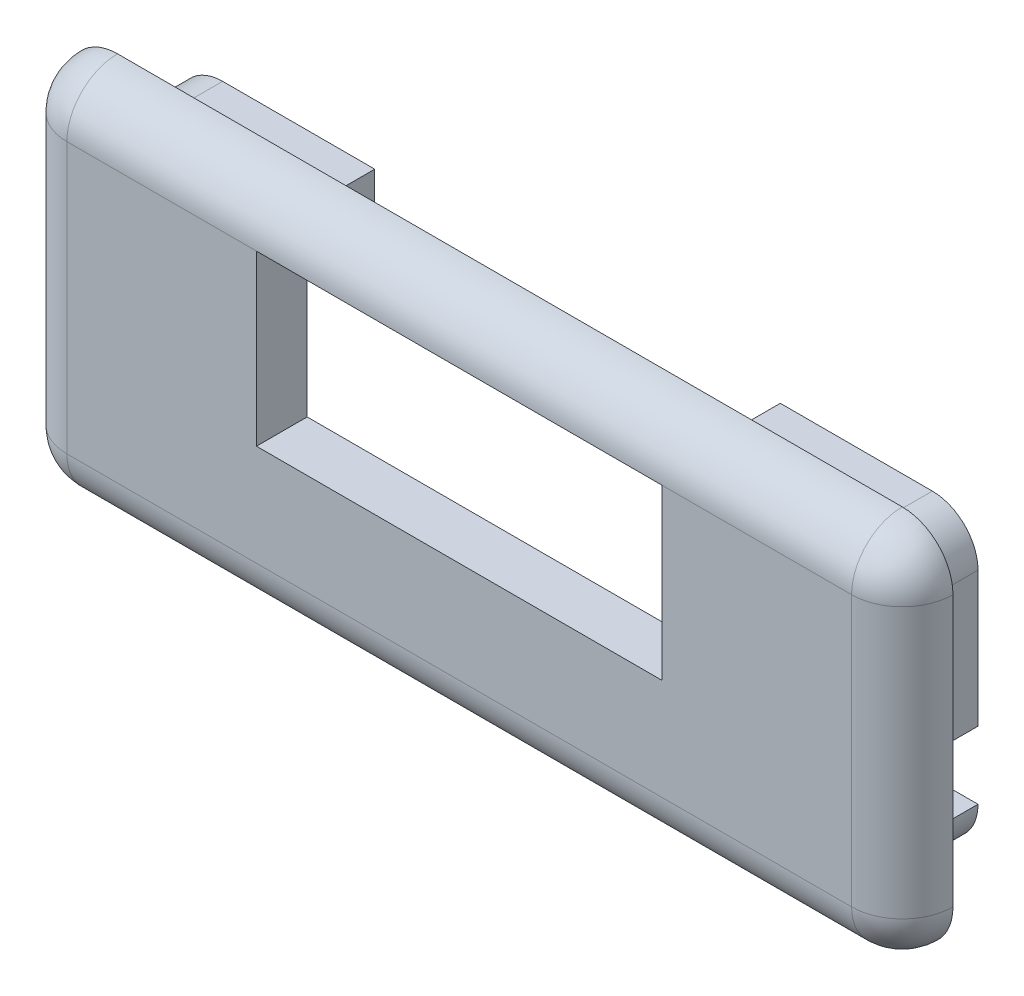
SolidWorks part; units mm, degrees
ref_plane "Front Plane" through (0, 0, 0) normal (0, 0, 1) x (1, 0, 0)
ref_plane "Top Plane" through (0, 0, 0) normal (0, 1, 0) x (1, 0, 0)
ref_plane "Right Plane" through (0, 0, 0) normal (1, 0, 0) x (0, 0, -1)
sketch "Sketch2" plane through (0, 0, 0) normal (0, 0, 1) x (1, 0, 0)
  line L0 (10.25, -0.4258) -> (15.1266, -0.4258) construction
  line L1 (10.25, 1.5742) -> (14.83, 1.5742) construction
  line L2 (11.85, -0.4258) -> (10.85, -0.4258)
  line L3 (11.85, 1.5742) -> (10.85, 1.5742)
  line L4 (10.85, 1.5742) -> (10.85, 5.5742)
  line L5 (10.5, 5.9242) -> (-10.5, 5.9242)
  line L6 (-10.85, 5.5742) -> (-10.85, 1.5742)
  line L7 (-10.5, -0.7758) -> (10.5, -0.7758)
  line L8 (11.85, -0.4258) -> (11.85, 5.5742)
  line L9 (10.5, 6.9242) -> (-10.5, 6.9242)
  line L10 (-11.85, 5.5742) -> (-11.85, -0.4258)
  line L11 (-10.5, -1.7758) -> (10.5, -1.7758)
  line L12 (11.85, 1.5742) -> (11.85, 5.5742)
  line L13 (10.5, 6.9242) -> (-10.5, 6.9242)
  line L14 (-11.85, 5.5742) -> (-11.85, 1.5742)
  line L15 (-10.5, -1.7758) -> (10.5, -1.7758)
  line L16 (-10.85, -0.4258) -> (-11.85, -0.4258)
  line L17 (-10.85, 1.5742) -> (-11.85, 1.5742)
  line L18 (0, 0) -> (0, 8.9306) construction
  line L19 (-10.85, 5.5742) -> (-10.85, -0.4258) construction
  line L20 (-11.85, 5.5742) -> (-11.85, -0.4258) construction
  line L21 (11.85, -0.4258) -> (11.85, 5.5742) construction
  line L22 (10.85, -0.4258) -> (10.85, 5.5742) construction
  arc A4 (10.85, 5.5742) -> (10.5, 5.9242) centre (10.5, 5.5742) ccw
  arc A5 (-10.5, 5.9242) -> (-10.85, 5.5742) centre (-10.5, 5.5742) ccw
  arc A6 (-10.85, -0.4258) -> (-10.5, -0.7758) centre (-10.5, -0.4258) ccw
  arc A7 (10.5, -0.7758) -> (10.85, -0.4258) centre (10.5, -0.4258) ccw
  arc A8 (10.5, -1.7758) -> (11.85, -0.4258) centre (10.5, -0.4258) ccw
  arc A9 (11.85, 5.5742) -> (10.5, 6.9242) centre (10.5, 5.5742) ccw
  arc A10 (-10.5, 6.9242) -> (-11.85, 5.5742) centre (-10.5, 5.5742) ccw
  arc A11 (-11.85, -0.4258) -> (-10.5, -1.7758) centre (-10.5, -0.4258) ccw
  arc A12 (10.5, -1.7758) -> (11.85, -0.4258) centre (10.5, -0.4258) ccw
  arc A13 (11.85, 5.5742) -> (10.5, 6.9242) centre (10.5, 5.5742) ccw
  arc A14 (-10.5, 6.9242) -> (-11.85, 5.5742) centre (-10.5, 5.5742) ccw
  arc A15 (-11.85, -0.4258) -> (-10.5, -1.7758) centre (-10.5, -0.4258) ccw
  dimension "D1" = 0.15
  dimension "D2" = 1
extrude "Boss-Extrude1" add sketch "Sketch2" against normal blind 2
sketch "Sketch3" plane through (0, 0, 0) normal (0, 0, 1) x (1, 0, 0)
  line L4 (11.6095, 8.0742) -> (-11.6095, 8.0742)
  line L5 (-13.1095, 6.5742) -> (-13.1095, -1.4258)
  line L6 (-11.6095, -2.9258) -> (11.6095, -2.9258)
  line L7 (13.1095, -1.4258) -> (13.1095, 6.5742)
  line L8 (11.6095, 8.0742) -> (-11.6095, 8.0742)
  line L9 (-13.1095, 6.5742) -> (-13.1095, -1.4258)
  line L10 (-11.6095, -2.9258) -> (11.6095, -2.9258)
  line L11 (13.1095, -1.4258) -> (13.1095, 6.5742)
  arc A4 (-11.6095, 8.0742) -> (-13.1095, 6.5742) centre (-11.6095, 6.5742) ccw
  arc A5 (-13.1095, -1.4258) -> (-11.6095, -2.9258) centre (-11.6095, -1.4258) ccw
  arc A6 (11.6095, -2.9258) -> (13.1095, -1.4258) centre (11.6095, -1.4258) ccw
  arc A7 (13.1095, 6.5742) -> (11.6095, 8.0742) centre (11.6095, 6.5742) ccw
  arc A8 (-11.6095, 8.0742) -> (-13.1095, 6.5742) centre (-11.6095, 6.5742) ccw
  arc A9 (-13.1095, -1.4258) -> (-11.6095, -2.9258) centre (-11.6095, -1.4258) ccw
  arc A10 (11.6095, -2.9258) -> (13.1095, -1.4258) centre (11.6095, -1.4258) ccw
  arc A11 (13.1095, 6.5742) -> (11.6095, 8.0742) centre (11.6095, 6.5742) ccw
  dimension "D1" = 0
extrude "Boss-Extrude2" add sketch "Sketch3" along normal blind 1.5
fillet "Fillet1" radius 1.5 8 edges at (12.6702, 7.6349, 1.5) (13.1095, 2.5742, 1.5) (12.6702, -2.4864, 1.5) (0, -2.9258, 1.5) (-12.6702, -2.4864, 1.5) (-13.1095, 2.5742, 1.5) (-12.6702, 7.6349, 1.5) (0, 8.0742, 1.5)
sketch "Sketch4" plane through (0, 0, 1.5) normal (0, 0, 1) x (1, 0, 0)
  line L0 (10.25, 1.5742) -> (-10.25, 1.5742) construction
  line L1 (10.25, 6.5742) -> (-10.25, 6.5742) construction
  line L4 (0, -1.4258) -> (0, 6.5742) construction
  line L5 (-11.6095, -1.4258) -> (11.6095, -1.4258) construction
  line L6 (11.6095, 6.5742) -> (-11.6095, 6.5742) construction
  line L7 (-6, -1.4258) -> (-6, 6.5742) construction
  line L8 (6, -1.4258) -> (6, 6.5742) construction
  line L10 (6, 1.5742) -> (-6, 1.5742)
  line L11 (6, 1.5742) -> (6, 6.5742)
  line L12 (6, 6.5742) -> (-6, 6.5742)
  line L13 (-6, 1.5742) -> (-6, 6.5742)
  dimension "D1" = 5
  dimension "D2" = 6
  dimension "D3" = 6
extrude "Cut-Extrude1" cut sketch "Sketch4" against normal up to vertex (1.5 mm away) up to point (-13.1095, 6.5742, 0)
sketch "Sketch5" plane through (0, 0, -2) normal (0, 0, -1) x (-1, 0, 0)
  line L0 (-10.5, 6.9242) -> (10.5, 6.9242) construction
  line L1 (-6, 5.9242) -> (6, 5.9242)
  line L2 (-6, 5.9242) -> (-6, 6.9242)
  line L3 (-6, 6.9242) -> (6, 6.9242)
  line L4 (6, 5.9242) -> (6, 6.9242)
extrude "Cut-Extrude2" cut sketch "Sketch5" against normal up to surface (2 mm away) up to face at (0, 4.3745, 0)
fillet "Fillet2" radius 0.25 9 edges at (10.7475, -0.6732, 0) (-10.7475, -0.6732, 0) (-10.85, 3.5742, 0) (-10.7475, 5.8217, 0) (10.85, 3.5742, 0) (10.7475, 5.8217, 0) (0, -0.7758, 0) (-8.25, 5.9242, 0) (8.25, 5.9242, 0)
